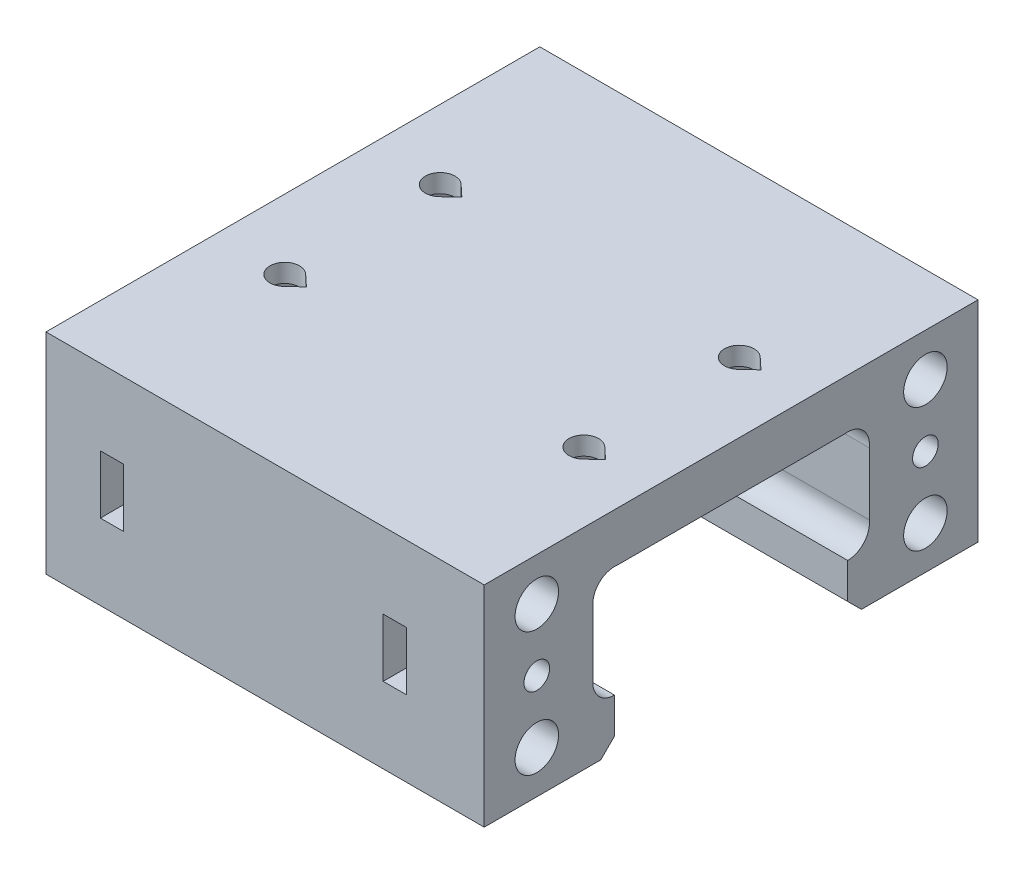
SolidWorks part; units mm, degrees
ref_plane "Front Plane" through (0, 0, 0) normal (0, 0, 1) x (1, 0, 0)
ref_plane "Top Plane" through (0, 0, 0) normal (0, 1, 0) x (1, 0, 0)
ref_plane "Right Plane" through (0, 0, 0) normal (1, 0, 0) x (0, 0, -1)
sketch "Sketch1" plane through (0, 0, 0) normal (1, 0, 0) x (0, 0, -1)
  line L0 (0, 0) -> (30, 0)
  line L1 (0, 0) -> (0, 5)
  line L2 (0, 5) -> (2.7781, 7.7781)
  line L3 (2.7781, 7.7781) -> (2.7781, 14.2781)
  line L4 (2.7781, 14.2781) -> (0, 14.2781) construction
  line L5 (0, 14.2781) -> (0, 23) construction
  line L6 (0, 23) -> (30, 23) construction
  line L12 (15, 0) -> (15, 23) construction
  line L13 (27.2219, 23) -> (2.7781, 23)
  line L14 (0, 20.2219) -> (0, 17.0562)
  line L15 (30, 14.2781) -> (30, 23) construction
  line L16 (27.2219, 14.2781) -> (30, 14.2781) construction
  line L17 (30, 20.2219) -> (30, 17.0562)
  line L18 (27.2219, 7.7781) -> (27.2219, 14.2781)
  line L19 (30, 5) -> (27.2219, 7.7781)
  line L20 (30, 0) -> (30, 5)
  arc A0 (2.7781, 14.2781) -> (0, 17.0562) centre (0, 14.2781) ccw
  arc A1 (0, 20.2219) -> (2.7781, 23) centre (0, 23) ccw
  arc A2 (30, 20.2219) -> (27.2219, 23) centre (30, 23) cw
  arc A3 (27.2219, 14.2781) -> (30, 17.0562) centre (30, 14.2781) cw
  dimension "D1" = 5.5563
  dimension "D2" = 15
  dimension "D3" = 23
  dimension "D4" = 45
  dimension "D5" = 6.5
  dimension "D6" = 5
sketch "Sketch2" plane through (0, 0, 0) normal (1, 0, 0) x (0, 0, -1)
  line L0 (-10, 26.6391) -> (-10, 32.1391) construction
  line L1 (15, 23) -> (15, -0.4684) construction
  line L2 (-10, 10.6391) -> (-10, 5.1391) construction
  line L3 (0, 25.7781) -> (30, 25.7781)
  line L4 (0, 11.5) -> (0, 6.9068)
  line L5 (0, 6.9068) -> (-1.7678, 5.1391)
  line L6 (-1.7678, 5.1391) -> (-16.7678, 5.1391)
  line L7 (-16.7678, 5.1391) -> (-16.7678, 32.1391)
  line L8 (-10, 26.6391) -> (0, 23) construction
  line L9 (0, 23) -> (0, 14.2781) construction
  line L10 (0, 14.2781) -> (-10, 10.6391) construction
  line L11 (-10, 10.6391) -> (-10, 26.6391) construction
  line L12 (0, 18.6391) -> (-10, 18.6391) construction
  line L13 (-16.7678, 32.1391) -> (46.7678, 32.1391)
  line L14 (15, 32.1391) -> (15, 25.7781) construction
  line L15 (-2.7781, 14.2781) -> (-2.7781, 23)
  line L16 (0, 5) -> (2.7781, 7.7781) construction
  line L17 (15, 0) -> (15, 23) construction
  line L18 (30, 18.6391) -> (40, 18.6391) construction
  line L19 (40, 10.6391) -> (40, 26.6391) construction
  line L20 (30, 14.2781) -> (40, 10.6391) construction
  line L21 (30, 23) -> (30, 14.2781) construction
  line L22 (40, 26.6391) -> (30, 23) construction
  line L23 (40, 10.6391) -> (40, 5.1391) construction
  line L24 (40, 26.6391) -> (40, 32.1391) construction
  line L25 (32.7781, 14.2781) -> (32.7781, 23)
  line L26 (46.7678, 5.1391) -> (46.7678, 32.1391)
  line L27 (31.7678, 5.1391) -> (46.7678, 5.1391)
  line L28 (30, 6.9068) -> (31.7678, 5.1391)
  line L29 (30, 11.5) -> (30, 6.9068)
  arc A0 (0, 25.7781) -> (-2.7781, 23) centre (0, 23) ccw
  arc A1 (-2.7781, 14.2781) -> (0, 11.5) centre (0, 14.2781) ccw
  arc A2 (2.7781, 14.2781) -> (0, 17.0562) centre (0, 14.2781) ccw construction
  circle A3 centre (-10, 26.6391) radius 2.7781
  circle A4 centre (-10, 10.6391) radius 2.7781
  circle A5 centre (40, 10.6391) radius 2.7781
  circle A6 centre (40, 26.6391) radius 2.7781
  arc A7 (32.7781, 14.2781) -> (30, 11.5) centre (30, 14.2781) cw
  arc A8 (30, 25.7781) -> (32.7781, 23) centre (30, 23) cw
  dimension "D1" = 10
  dimension "D2" = 16
  dimension "D3" = 15
  dimension "D4" = 27
  dimension "D5" = 2.5
extrude "Boss-Extrude2" add sketch "Sketch2" along normal blind 56.3836
sketch "Sketch3" plane through (56.3836, 0, 0) normal (1, 0, 0) x (0, 0, -1)
  line L0 (-10, 26.6391) -> (-10, 10.6391) construction
  line L1 (15, 20.921) -> (15, 13.7492) construction
  line L2 (15, 200023) -> (15, -200000.4684) construction
  line L3 (-10, 18.6391) -> (15, 18.6391) construction
  circle A0 centre (-10, 18.6391) radius 1.651
  circle A1 centre (40, 18.6391) radius 1.651
  dimension "D1" = 3.302
extrude "Cut-Extrude1" cut sketch "Sketch3" against normal blind 23.5668
ref_plane "Plane1" through (14.3012, 0, 0) normal (1, 0, 0) x (0, 0, -1)
ref_plane "Plane2" through (0, 18.6391, 0) normal (0, -1, 0) x (0, 0, -1)
ref_axis "Axis1" through (-60.3203, 18.6391, 10) along (1, 0, 0)
ref_axis "Axis2" through (56.3836, 18.6391, -40) along (1, 0, 0)
sketch "Sketch4" plane through (0, 18.6391, 0) normal (0, -1, 0) x (0, 0, -1)
  line L0 (-16.7678, 56.3836) -> (-16.7678, 0) construction
  line L1 (-16.7678, 46.3836) -> (-6, 46.3836)
  line L2 (-16.7678, 46.3836) -> (-16.7678, 43.3836)
  line L3 (-16.7678, 43.3836) -> (-6, 43.3836)
  line L4 (-6, 46.3836) -> (-6, 43.3836)
  line L5 (46.7678, 56.3836) -> (46.7678, 0) construction
  line L6 (46.7678, 46.3836) -> (36, 46.3836)
  line L7 (46.7678, 46.3836) -> (46.7678, 43.3836)
  line L8 (46.7678, 43.3836) -> (36, 43.3836)
  line L9 (36, 46.3836) -> (36, 43.3836)
  line L10 (-16.7678, 56.3836) -> (-1.7678, 56.3836) construction
  line L11 (-16.7678, 7) -> (-6, 7)
  line L12 (-16.7678, 7) -> (-16.7678, 10)
  line L13 (-16.7678, 10) -> (-6, 10)
  line L14 (-6, 7) -> (-6, 10)
  line L15 (36, 7) -> (46.7678, 7)
  line L16 (36, 7) -> (36, 10)
  line L17 (36, 10) -> (46.7678, 10)
  line L18 (46.7678, 7) -> (46.7678, 10)
  line L19 (-16.7678, 0) -> (-1.7678, 0) construction
  line L20 (-10, -60.3203) -> (-10, 103.1706) construction
  dimension "D1" = 10
  dimension "D2" = 10
  dimension "D3" = 4
  dimension "D4" = 3
extrude "Cut-Extrude2" cut sketch "Sketch4" against normal mid plane 7.5
sketch "Sketch5" plane through (56.3836, 0, 0) normal (1, 0, 0) x (0, 0, -1)
  circle A0 centre (-10, 26.6391) radius 2.8
  circle A1 centre (0, 23) radius 2.8
  circle A2 centre (-10, 10.6391) radius 2.8
  circle A3 centre (40, 26.6391) radius 2.8
  circle A4 centre (40, 10.6391) radius 2.8
  circle A5 centre (30, 23) radius 2.8
  circle A6 centre (0, 14.2781) radius 2.8
  circle A7 centre (30, 14.2781) radius 2.8
  arc A8 (0, 25.7781) -> (-2.7781, 23) centre (0, 23) ccw construction
  arc A9 (-2.7781, 14.2781) -> (0, 11.5) centre (0, 14.2781) ccw construction
  arc A10 (30, 11.5) -> (32.7781, 14.2781) centre (30, 14.2781) ccw construction
  arc A11 (32.7781, 23) -> (30, 25.7781) centre (30, 23) ccw construction
  dimension "D1" = 5.6
extrude "Cut-Extrude3" cut sketch "Sketch5" against normal through all
ref_plane "Plane3" through (28.1918, 0, 0) normal (-1, 0, 0) x (0, 0, 1)
mirror "Mirror1" about plane through (28.1918, 0, 0) normal (-1, 0, 0) of "Cut-Extrude1"
sketch "Sketch6" plane through (0, 25.7781, 0) normal (0, -1, 0) x (1, 0, 0)
  line L0 (0, -0.3493) -> (56.3836, -29.6507) construction
  line L1 (56.3836, -0.3493) -> (0, -29.6507) construction
  line L2 (11.738, -5) -> (10.2504, -3.6087)
  line L3 (47.4344, -25) -> (8.9491, -25) construction
  line L4 (47.4344, -25) -> (47.4344, -5) construction
  line L5 (47.4344, -5) -> (8.9491, -5) construction
  line L6 (8.9491, -25) -> (8.9491, -5) construction
  line L7 (47.4344, -25) -> (8.9491, -5) construction
  line L8 (47.4344, -5) -> (8.9491, -25) construction
  line L9 (11.738, -5) -> (10.2504, -6.3913)
  line L10 (8.9491, -15) -> (47.4344, -15) construction
  line L11 (50.2233, -5) -> (48.7357, -3.6087)
  line L12 (50.2233, -5) -> (48.7357, -6.3913)
  line L13 (85.9197, -5) -> (47.4344, -5) construction
  line L14 (50.2233, -25) -> (48.7357, -26.3913)
  line L15 (50.2233, -25) -> (48.7357, -23.6087)
  line L16 (11.738, -25) -> (10.2504, -23.6087)
  line L17 (11.738, -25) -> (10.2504, -26.3913)
  arc A0 (10.2504, -3.6087) -> (10.2504, -6.3913) centre (8.9491, -5) ccw
  arc A1 (48.7357, -3.6087) -> (48.7357, -6.3913) centre (47.4344, -5) ccw
  arc A2 (48.7357, -23.6087) -> (48.7357, -26.3913) centre (47.4344, -25) ccw
  arc A3 (10.2504, -23.6087) -> (10.2504, -26.3913) centre (8.9491, -25) ccw
  point P8 (28.1918, -15)
  point P22 (49.4795, -4.3043)
  point P28 (49.4795, -25.6957)
  dimension "D1" = 3.81
  dimension "D2" = 20
  dimension "D3" = 2
extrude "Cut-Extrude4" cut sketch "Sketch6" against normal through all
sketch "Sketch7" plane through (0, 25.7781, 0) normal (0, -1, 0) x (-1, 0, 0)
  line L1 (-10.9215, 28.4163) -> (-12.8939, 25)
  line L2 (-12.8939, 25) -> (-10.9215, 21.5837)
  line L3 (-10.9215, 21.5837) -> (-6.9767, 21.5837)
  line L4 (-6.9767, 21.5837) -> (-5.0043, 25)
  line L5 (-5.0043, 25) -> (-6.9767, 28.4163)
  line L6 (-6.9767, 28.4163) -> (-10.9215, 28.4163)
  line L7 (-10.9215, 8.4163) -> (-12.8939, 5)
  line L8 (-12.8939, 5) -> (-10.9215, 1.5837)
  line L9 (-10.9215, 1.5837) -> (-6.9767, 1.5837)
  line L10 (-6.9767, 1.5837) -> (-5.0043, 5)
  line L11 (-5.0043, 5) -> (-6.9767, 8.4163)
  line L12 (-6.9767, 8.4163) -> (-10.9215, 8.4163)
  line L13 (-45.462, 8.4163) -> (-49.4068, 8.4163)
  line L14 (-49.4068, 8.4163) -> (-51.3792, 5)
  line L15 (-51.3792, 5) -> (-49.4068, 1.5837)
  line L16 (-49.4068, 1.5837) -> (-45.462, 1.5837)
  line L17 (-45.462, 1.5837) -> (-43.4896, 5)
  line L18 (-43.4896, 5) -> (-45.462, 8.4163)
  line L19 (-45.462, 28.4163) -> (-49.4068, 28.4163)
  line L20 (-49.4068, 28.4163) -> (-51.3792, 25)
  line L21 (-51.3792, 25) -> (-49.4068, 21.5837)
  line L22 (-49.4068, 21.5837) -> (-45.462, 21.5837)
  line L23 (-45.462, 21.5837) -> (-43.4896, 25)
  line L24 (-43.4896, 25) -> (-45.462, 28.4163)
  circle A0 centre (-8.9491, 25) radius 3.4163 construction
  circle A1 centre (-8.9491, 5) radius 3.4163 construction
  circle A2 centre (-47.4344, 5) radius 3.4163 construction
  circle A3 centre (-47.4344, 25) radius 3.4163 construction
  point P28 (-50.1977, 27.9051)
  point P37 (0, 0)
  dimension "D1" = 6.8326
extrude "Cut-Extrude5" cut sketch "Sketch7" against normal blind 4
